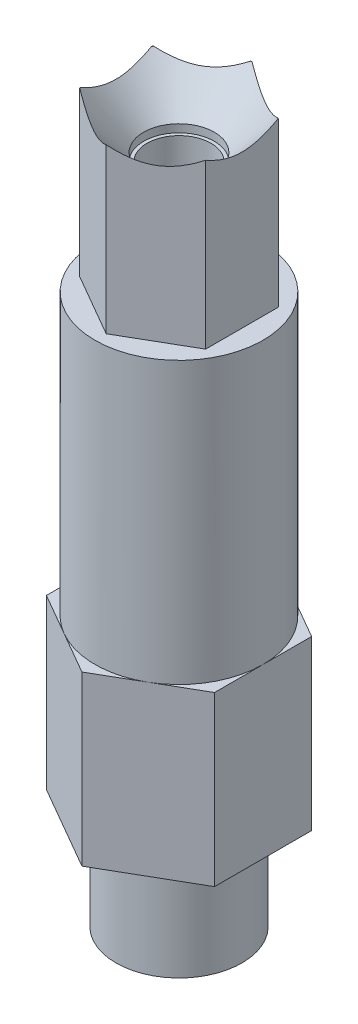
SolidWorks part; units mm, degrees
material "7075-T6 (SN)"
ref_plane "Front Plane" through (0, 0, 0) normal (0, 0, 1) x (1, 0, 0)
ref_plane "Top Plane" through (0, 0, 0) normal (0, 1, 0) x (1, 0, 0)
ref_plane "Right Plane" through (0, 0, 0) normal (1, 0, 0) x (0, 0, -1)
sketch "Sketch1" plane through (0, 0, 0) normal (0, 1, 0) x (1, 0, 0)
  line L1 (6.35, -3.6662) -> (6.35, 3.6662)
  line L2 (6.35, 3.6662) -> (0, 7.3323)
  line L3 (0, 7.3323) -> (-6.35, 3.6662)
  line L4 (-6.35, 3.6662) -> (-6.35, -3.6662)
  line L5 (-6.35, -3.6662) -> (0, -7.3323)
  line L6 (0, -7.3323) -> (6.35, -3.6662)
  circle A0 centre (0, 0) radius 6.35 construction
  dimension "D1" = 12.7
extrude "Boss-Extrude1" add sketch "Sketch1" along normal blind 12.7
sketch "Sketch2" plane through (0, 0, 0) normal (0, -1, 0) x (1, 0, 0)
  circle A0 centre (0, 0) radius 4.7625
  dimension "D1" = 9.525
extrude "Boss-Extrude2" add sketch "Sketch2" along normal blind 7.62
sketch "Sketch3" plane through (0, 12.7, 0) normal (0, 1, 0) x (1, 0, 0)
  circle A0 centre (0, 0) radius 6.35
  dimension "D1" = 12.7
extrude "Boss-Extrude3" add sketch "Sketch3" along normal blind 33.528
sketch "Sketch4" plane through (0, 46.228, 0) normal (0, 1, 0) x (1, 0, 0)
  line L0 (-5.08, 3.81) -> (5.08, 3.81)
  circle A0 centre (0, 0) radius 6.35 construction
  arc A1 (5.08, 3.81) -> (-5.08, 3.81) centre (0, 0) ccw
  dimension "D1" = 3.81
extrude "Cut-Extrude1" [suppressed] cut sketch "Sketch4" against normal blind 25.4
ref_axis "Axis1" through (0, 46.228, 0) along (0, -1, 0)
hole_wizard " Tapped Hole1" positions "Sketch5" profile "Sketch6" tap size "#10-32" standard "ANSI Inch"
sketch "Sketch5" plane through (0, 46.228, 0) normal (0, 1, 0) x (1, 0, 0)
  point P0 (0, 0)
sketch "Sketch6" plane through (0, 46.228, 0) normal (1, 0, 0) x (0, 0, 1)
  line L0 (0, 0) -> (0, 20.2633)
  line L1 (0, 20.2633) -> (2.0193, 19.05)
  line L2 (2.0193, 19.05) -> (2.0193, 16.002)
  line L3 (2.0193, 16.002) -> (2.413, 16.002)
  line L5 (2.413, 16.002) -> (2.413, 3.5063)
  line L6 (2.413, 3.5063) -> (5.461, 0)
  line L7 (5.461, 0) -> (0, 0)
  line L8 (-2.413, 3.5063) -> (-5.461, 0) construction
  line L10 (0, 20.2633) -> (-2.0193, 19.05) construction
  line L11 (0, -6.35) -> (0, 107.95) construction
  dimension "Tap Drill Dia." = 4.0386
  dimension "Tap Drill Depth" = 19.05
  dimension "Thread Major Dia." = 4.826
  dimension "Thread Depth" = 16.002
  dimension "Near C'Sink Dia." = 10.922
  dimension "Near C'Sink Angle" = 82
  dimension "Drill Angle" = 118
sketch "Sketch7" plane through (0, -7.62, 0) normal (0, -1, 0) x (1, 0, 0)
  circle A0 centre (0, 0) radius 3
  dimension "D1" = 6
extrude "Cut-Extrude2" [suppressed] cut sketch "Sketch7" against normal blind 2.54 contours A0
sketch "Sketch8" plane through (0, 46.228, 0) normal (0, 1, 0) x (1, 0, 0)
  line L1 (-4.7625, -2.7496) -> (0, -5.4993)
  line L2 (0, -5.4993) -> (4.7625, -2.7496)
  line L3 (4.7625, -2.7496) -> (4.7625, 2.7496)
  line L4 (4.7625, 2.7496) -> (0, 5.4993)
  line L5 (0, 5.4993) -> (-4.7625, 2.7496)
  line L6 (-4.7625, 2.7496) -> (-4.7625, -2.7496)
  circle A0 centre (0, 0) radius 4.7625 construction
  circle A1 centre (0, 0) radius 6.35 construction
  circle A2 centre (0, 0) radius 6.35
  dimension "D1" = 9.525
extrude "Cut-Extrude3" cut sketch "Sketch8" against normal blind 12.319
ref_plane "Plane1" through (0, 46.228, 0) normal (0, -1, 0) x (-1, 0, 0)
sketch "Sketch9" plane through (0, 46.228, 0) normal (0, -1, 0) x (-1, 0, 0)
  circle A0 centre (0, 0) radius 2.667
  dimension "D1" = 5.334
extrude "Cut-Extrude4" cut sketch "Sketch9" along normal blind 3.81
